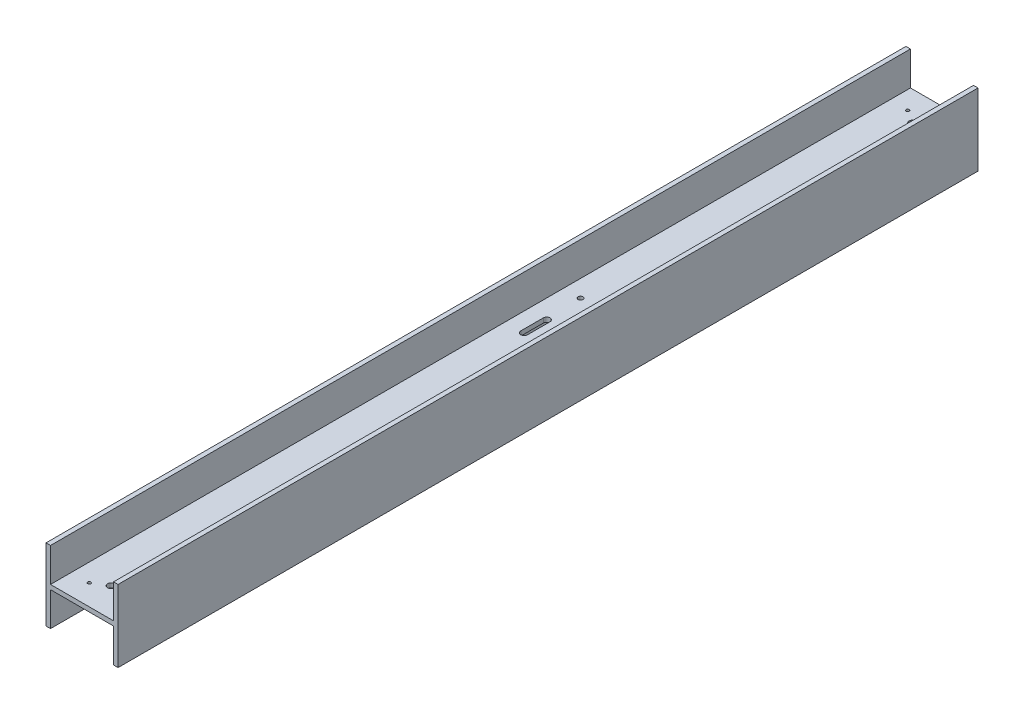
SolidWorks part; units mm, degrees
material "6061 Alloy"
ref_plane "Front Plane" through (0, 0, 0) normal (0, 0, 1) x (1, 0, 0)
ref_plane "Top Plane" through (0, 0, 0) normal (0, 1, 0) x (1, 0, 0)
ref_plane "Right Plane" through (0, 0, 0) normal (1, 0, 0) x (0, 0, -1)
ref_axis "Axis1" through (0, 27.94, 0) along (0, -1, 0)
sketch "Sketch1" plane through (0, 0, 0) normal (0, 0, 1) x (1, 0, 0)
  line L0 (25.4, 0) -> (-25.4, 0) construction
  line L1 (-25.4, -25.4) -> (-25.4, 25.4)
  line L2 (0, -18.7284) -> (0, 18.7284) construction
  line L3 (25.4, -25.4) -> (25.4, 25.4)
  line L4 (-25.4, 25.4) -> (-22.225, 25.4)
  line L5 (-22.225, 25.4) -> (-22.225, 1.5875)
  line L6 (-22.225, 1.5875) -> (22.225, 1.5875)
  line L7 (25.4, 25.4) -> (22.225, 25.4)
  line L8 (22.225, 25.4) -> (22.225, 1.5875)
  line L9 (0, 0) -> (52.8982, 0) construction
  line L10 (22.225, -25.4) -> (22.225, -1.5875)
  line L11 (25.4, -25.4) -> (22.225, -25.4)
  line L12 (-22.225, -1.5875) -> (22.225, -1.5875)
  line L13 (-22.225, -25.4) -> (-22.225, -1.5875)
  line L14 (-25.4, -25.4) -> (-22.225, -25.4)
  point P12 (0, 1.5875)
  point P20 (0, -1.5875)
  dimension "D1" = 44.45
  dimension "D2" = 50.8
  dimension "D3" = 3.175
  dimension "D4" = 3.175
extrude "Extrusion Profile" add sketch "Sketch1" along normal mid plane 606.425
sketch "Sketch3" plane through (0, 1.5875, 0) normal (0, 1, 0) x (1, 0, 0)
  circle A1 centre (10.16, -58.547) radius 1.7272
  circle A3 centre (-10.16, 58.547) radius 1.7272
  dimension "D1" = 3.4544
  dimension "D2" = 10.16
  dimension "D3" = 58.547
  dimension "D4" = 117.094
  dimension "D5" = 20.32
extrude "Thru Holes for Driver Enclosure" cut sketch "Sketch3" against normal through all
sketch "Sketch4" plane through (0, -1.5875, 0) normal (0, -1, 0) x (1, 0, 0)
  line L0 (-8.89, -33.3375) -> (-8.89, -17.4625) construction
  line L1 (-11.2712, -33.3375) -> (-11.2712, -17.4625)
  line L2 (-6.5087, -33.3375) -> (-6.5087, -17.4625)
  arc A2 (-11.2712, -33.3375) -> (-6.5087, -33.3375) centre (-8.89, -33.3375) ccw
  arc A3 (-6.5087, -17.4625) -> (-11.2712, -17.4625) centre (-8.89, -17.4625) ccw
  point P5 (-8.89, -25.4)
  dimension "D1" = 15.875
  dimension "D2" = 4.7625
  dimension "D3" = 8.89
  dimension "D4" = 25.4
extrude "Wire Routing Slot" cut sketch "Sketch4" against normal through all
sketch "Sketch5" plane through (0, 1.5875, 0) normal (0, 1, 0) x (1, 0, 0)
  line L1 (0, 0) -> (-153.8737, 0) construction
  line L2 (0, 0) -> (0, -405.4052) construction
  circle A0 centre (-9.525, -288.544) radius 1.0922
  circle A1 centre (9.525, -288.544) radius 1.0922
  circle A2 centre (9.525, 288.544) radius 1.0922
  circle A3 centre (-9.525, 288.544) radius 1.0922
  dimension "D1" = 2.1844
  dimension "D2" = 19.05
  dimension "D3" = 288.544
extrude "4-40 Tapped Holes for Magnetic Catch" cut sketch "Sketch5" against normal through all
sketch "Sketch for Mounting Bracket Hole" plane through (0, 1.5875, 0) normal (0, 1, 0) x (1, 0, 0)
  circle A0 centre (0, -282.575) radius 3.175 construction
  dimension "D1" = 6.35
  dimension "D2" = 282.575
hole_wizard "1/4-20 Tapped Hole for Mounting Bracket" positions "Sketch8" profile "Sketch7" tap size "1/4-20" standard "ANSI Inch" end condition through all
sketch "Sketch8" plane through (0, 1.5875, 0) normal (0, 1, 0) x (1, 0, 0)
  point P0 (0, -282.575)
sketch "Sketch7" plane through (0, 1.5875, 282.575) normal (1, 0, 0) x (0, 0, 1)
  line L0 (0, 0) -> (0, 26.9875)
  line L1 (0, 26.9875) -> (2.5527, 26.9875)
  line L2 (2.5527, 26.9875) -> (2.5527, 0)
  line L5 (2.5527, 0) -> (0, 0)
  line L11 (0, -6.35) -> (0, 107.95) construction
  dimension "Thru Tap Drill Dia." = 5.1054
  dimension "Thru Tap Drill Depth" = 26.9875
cosmetic thread "Hole Thread1" parameters "D2"=6.35
mirror "Mirror1" about plane through (0, 0, 0) normal (0, 0, 1) of "1/4-20 Tapped Hole for Mounting Bracket"
sketch "Sketch9" plane through (0, -1.5875, 0) normal (0, -1, 0) x (1, 0, 0)
  line L0 (0, 228.6) -> (0, 146.05) construction
  line L1 (0, 146.05) -> (0, 0) construction
  line L2 (0, 0) -> (0, -146.05) construction
  line L3 (0, -146.05) -> (0, -228.6) construction
  circle A0 centre (0, -228.6) radius 1.0922
  circle A1 centre (0, -146.05) radius 1.0922
  circle A2 centre (0, 146.05) radius 1.0922
  circle A3 centre (0, 228.6) radius 1.0922
  dimension "D1" = 2.1844
  dimension "D2" = 82.55
  dimension "D3" = 146.05
extrude "4-40 Tapped Holes for LED Board" cut sketch "Sketch9" against normal through all
